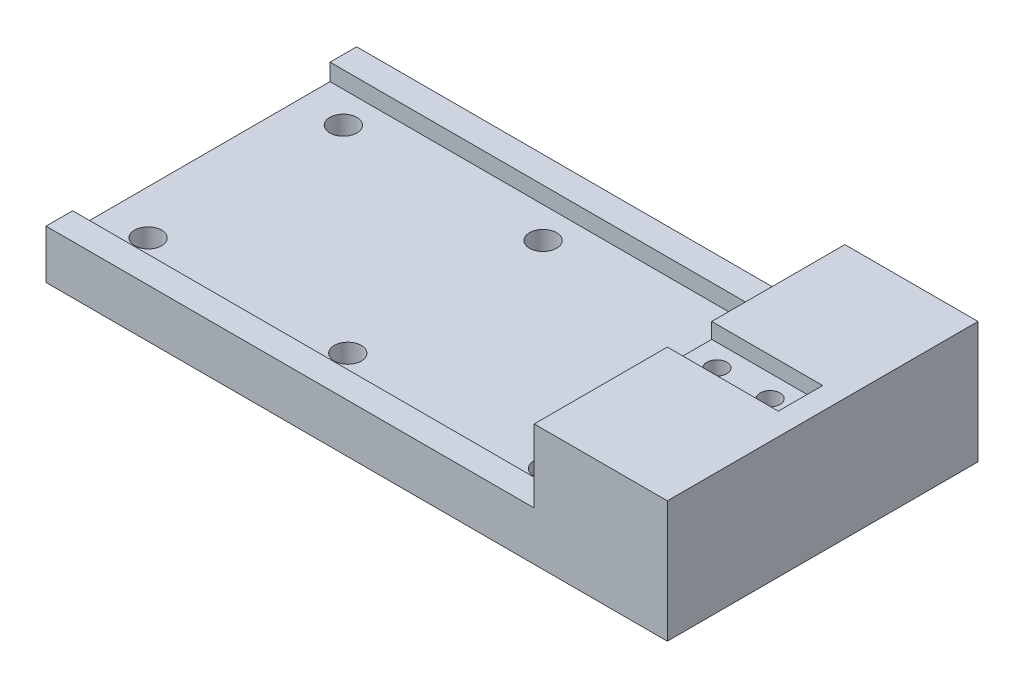
SolidWorks part; units mm, degrees
note: The reader was unsure of these and kept them because the rebuilt part matched: shared geometry of "Esquisse12<3>".
ref_plane "Plan de face" through (0, 0, 0) normal (0, 0, 1) x (1, 0, 0)
ref_plane "Plan de dessus" through (0, 0, 0) normal (0, 1, 0) x (1, 0, 0)
ref_plane "Plan de droite" through (0, 0, 0) normal (1, 0, 0) x (0, 0, -1)
sketch "Esquisse1" plane through (0, 0, 0) normal (0, 0, 1) x (1, 0, 0)
  line L1 (-70, 5.5) -> (70, 5.5)
  line L2 (-70, 5.5) -> (-70, -5.5)
  line L3 (-70, -5.5) -> (70, -5.5)
  line L4 (70, 5.5) -> (70, -5.5)
  line L5 (-70, 5.5) -> (70, -5.5) construction
  line L6 (-70, -5.5) -> (70, 5.5) construction
  point P0 (0, 0)
  dimension "D1" = 11
  dimension "D2" = 140
extrude "Boss.-Extru.1" add sketch "Esquisse1" along normal blind 70
chamfer "Chanfrein1" [suppressed] distance 20 angle 75
sketch "Esquisse2" plane through (-70, 0, 0) normal (-1, 0, 0) x (0, 0, 1)
  line L0 (70, 5.5) -> (0, 5.5) construction
  line L1 (25.6, 5.5) -> (44.4, 5.5)
  arc A0 (25.6, 5.5) -> (44.4, 5.5) centre (35, 5.5) ccw
  dimension "D1" = 9.4
extrude "Enlèv. mat.-Extru.1" cut sketch "Esquisse2" against normal offset from surface (110 mm away) 30 up to face at (70, 0, 35)
sketch "Esquisse4" plane through (0, 5.5, 0) normal (0, 1, 0) x (1, 0, 0)
  line L0 (-69, -18.1) -> (-69, -24.1)
  line L1 (-9, -18.1) -> (-9, -24.1)
  line L2 (-70, -35) -> (70, -35) construction
  line L3 (-70, -25.6) -> (-70, -44.4) construction
  line L4 (70, -70) -> (70, 0) construction
  line L5 (-70, -25.6) -> (-70, 0) construction
  line L6 (-69, -51.9) -> (-69, -45.9)
  line L7 (-68, -18.1) -> (-68, -24.1)
  line L8 (-68, -51.9) -> (-68, -45.9)
  line L9 (-67, -18.1) -> (-67, -24.1)
  line L10 (-67, -51.9) -> (-67, -45.9)
  line L11 (-66, -18.1) -> (-66, -24.1)
  line L12 (-66, -51.9) -> (-66, -45.9)
  line L13 (-65, -18.1) -> (-65, -24.1)
  line L14 (-65, -51.9) -> (-65, -45.9)
  line L15 (-64, -18.1) -> (-64, -24.1)
  line L16 (-64, -51.9) -> (-64, -45.9)
  line L17 (-63, -18.1) -> (-63, -24.1)
  line L18 (-63, -51.9) -> (-63, -45.9)
  line L19 (-62, -18.1) -> (-62, -24.1)
  line L20 (-62, -51.9) -> (-62, -45.9)
  line L21 (-61, -18.1) -> (-61, -24.1)
  line L22 (-61, -51.9) -> (-61, -45.9)
  line L23 (-60, -18.1) -> (-60, -24.1)
  line L24 (-60, -51.9) -> (-60, -45.9)
  line L25 (-59, -18.1) -> (-59, -24.1)
  line L26 (-59, -51.9) -> (-59, -45.9)
  line L27 (-58, -18.1) -> (-58, -24.1)
  line L28 (-58, -51.9) -> (-58, -45.9)
  line L29 (-57, -18.1) -> (-57, -24.1)
  line L30 (-57, -51.9) -> (-57, -45.9)
  line L31 (-56, -18.1) -> (-56, -24.1)
  line L32 (-56, -51.9) -> (-56, -45.9)
  line L33 (-55, -18.1) -> (-55, -24.1)
  line L34 (-55, -51.9) -> (-55, -45.9)
  line L35 (-54, -18.1) -> (-54, -24.1)
  line L36 (-54, -51.9) -> (-54, -45.9)
  line L37 (-53, -18.1) -> (-53, -24.1)
  line L38 (-53, -51.9) -> (-53, -45.9)
  line L39 (-52, -18.1) -> (-52, -24.1)
  line L40 (-52, -51.9) -> (-52, -45.9)
  line L41 (-51, -18.1) -> (-51, -24.1)
  line L42 (-51, -51.9) -> (-51, -45.9)
  line L43 (-50, -18.1) -> (-50, -24.1)
  line L44 (-50, -51.9) -> (-50, -45.9)
  line L45 (-49, -18.1) -> (-49, -24.1)
  line L46 (-49, -51.9) -> (-49, -45.9)
  line L47 (-48, -18.1) -> (-48, -24.1)
  line L48 (-48, -51.9) -> (-48, -45.9)
  line L49 (-47, -18.1) -> (-47, -24.1)
  line L50 (-47, -51.9) -> (-47, -45.9)
  line L51 (-46, -18.1) -> (-46, -24.1)
  line L52 (-46, -51.9) -> (-46, -45.9)
  line L53 (-45, -18.1) -> (-45, -24.1)
  line L54 (-45, -51.9) -> (-45, -45.9)
  line L55 (-44, -18.1) -> (-44, -24.1)
  line L56 (-44, -51.9) -> (-44, -45.9)
  line L57 (-43, -18.1) -> (-43, -24.1)
  line L58 (-43, -51.9) -> (-43, -45.9)
  line L59 (-42, -18.1) -> (-42, -24.1)
  line L60 (-42, -51.9) -> (-42, -45.9)
  line L61 (-41, -18.1) -> (-41, -24.1)
  line L62 (-41, -51.9) -> (-41, -45.9)
  line L63 (-40, -18.1) -> (-40, -24.1)
  line L64 (-40, -51.9) -> (-40, -45.9)
  line L65 (-39, -18.1) -> (-39, -24.1)
  line L66 (-39, -51.9) -> (-39, -45.9)
  line L67 (-38, -18.1) -> (-38, -24.1)
  line L68 (-38, -51.9) -> (-38, -45.9)
  line L69 (-37, -18.1) -> (-37, -24.1)
  line L70 (-37, -51.9) -> (-37, -45.9)
  line L71 (-36, -18.1) -> (-36, -24.1)
  line L72 (-36, -51.9) -> (-36, -45.9)
  line L73 (-35, -18.1) -> (-35, -24.1)
  line L74 (-35, -51.9) -> (-35, -45.9)
  line L75 (-34, -18.1) -> (-34, -24.1)
  line L76 (-34, -51.9) -> (-34, -45.9)
  line L77 (-33, -18.1) -> (-33, -24.1)
  line L78 (-33, -51.9) -> (-33, -45.9)
  line L79 (-32, -18.1) -> (-32, -24.1)
  line L80 (-32, -51.9) -> (-32, -45.9)
  line L81 (-31, -18.1) -> (-31, -24.1)
  line L82 (-31, -51.9) -> (-31, -45.9)
  line L83 (-30, -18.1) -> (-30, -24.1)
  line L84 (-30, -51.9) -> (-30, -45.9)
  line L85 (-29, -18.1) -> (-29, -24.1)
  line L86 (-29, -51.9) -> (-29, -45.9)
  line L87 (-28, -18.1) -> (-28, -24.1)
  line L88 (-28, -51.9) -> (-28, -45.9)
  line L89 (-27, -18.1) -> (-27, -24.1)
  line L90 (-27, -51.9) -> (-27, -45.9)
  line L91 (-26, -18.1) -> (-26, -24.1)
  line L92 (-26, -51.9) -> (-26, -45.9)
  line L93 (-25, -18.1) -> (-25, -24.1)
  line L94 (-25, -51.9) -> (-25, -45.9)
  line L95 (-24, -18.1) -> (-24, -24.1)
  line L96 (-24, -51.9) -> (-24, -45.9)
  line L97 (-23, -18.1) -> (-23, -24.1)
  line L98 (-23, -51.9) -> (-23, -45.9)
  line L99 (-22, -18.1) -> (-22, -24.1)
  line L100 (-22, -51.9) -> (-22, -45.9)
  line L101 (-21, -18.1) -> (-21, -24.1)
  line L102 (-21, -51.9) -> (-21, -45.9)
  line L103 (-20, -18.1) -> (-20, -24.1)
  line L104 (-20, -51.9) -> (-20, -45.9)
  line L105 (-19, -18.1) -> (-19, -24.1)
  line L106 (-19, -51.9) -> (-19, -45.9)
  line L107 (-18, -18.1) -> (-18, -24.1)
  line L108 (-18, -51.9) -> (-18, -45.9)
  line L109 (-17, -18.1) -> (-17, -24.1)
  line L110 (-17, -51.9) -> (-17, -45.9)
  line L111 (-16, -18.1) -> (-16, -24.1)
  line L112 (-16, -51.9) -> (-16, -45.9)
  line L113 (-15, -18.1) -> (-15, -24.1)
  line L114 (-15, -51.9) -> (-15, -45.9)
  line L115 (-14, -18.1) -> (-14, -24.1)
  line L116 (-14, -51.9) -> (-14, -45.9)
  line L117 (-13, -18.1) -> (-13, -24.1)
  line L118 (-13, -51.9) -> (-13, -45.9)
  line L119 (-12, -18.1) -> (-12, -24.1)
  line L120 (-12, -51.9) -> (-12, -45.9)
  line L121 (-11, -18.1) -> (-11, -24.1)
  line L122 (-11, -51.9) -> (-11, -45.9)
  line L123 (-10, -18.1) -> (-10, -24.1)
  line L124 (-10, -51.9) -> (-10, -45.9)
  line L125 (40, -25.6) -> (-70, -25.6) construction
  line L126 (-9, -51.9) -> (-9, -45.9)
  line L127 (-8, -18.1) -> (-8, -24.1)
  line L128 (-8, -51.9) -> (-8, -45.9)
  line L129 (-7, -18.1) -> (-7, -24.1)
  line L130 (-7, -51.9) -> (-7, -45.9)
  line L131 (-6, -18.1) -> (-6, -24.1)
  line L132 (-6, -51.9) -> (-6, -45.9)
  line L133 (-5, -18.1) -> (-5, -24.1)
  line L134 (-5, -51.9) -> (-5, -45.9)
  line L135 (-4, -18.1) -> (-4, -24.1)
  line L136 (-4, -51.9) -> (-4, -45.9)
  line L137 (-3, -18.1) -> (-3, -24.1)
  line L138 (-3, -51.9) -> (-3, -45.9)
  line L139 (-2, -18.1) -> (-2, -24.1)
  line L140 (-2, -51.9) -> (-2, -45.9)
  line L141 (-1, -18.1) -> (-1, -24.1)
  line L142 (-1, -51.9) -> (-1, -45.9)
  line L143 (0, -18.1) -> (0, -24.1)
  line L144 (0, -51.9) -> (0, -45.9)
  line L145 (1, -18.1) -> (1, -24.1)
  line L146 (1, -51.9) -> (1, -45.9)
  line L147 (2, -18.1) -> (2, -24.1)
  line L148 (2, -51.9) -> (2, -45.9)
  line L149 (3, -18.1) -> (3, -24.1)
  line L150 (3, -51.9) -> (3, -45.9)
  line L151 (4, -18.1) -> (4, -24.1)
  line L152 (4, -51.9) -> (4, -45.9)
  line L153 (5, -18.1) -> (5, -24.1)
  line L154 (5, -51.9) -> (5, -45.9)
  line L155 (6, -18.1) -> (6, -24.1)
  line L156 (6, -51.9) -> (6, -45.9)
  line L157 (7, -18.1) -> (7, -24.1)
  line L158 (7, -51.9) -> (7, -45.9)
  line L159 (8, -18.1) -> (8, -24.1)
  line L160 (8, -51.9) -> (8, -45.9)
  line L161 (9, -18.1) -> (9, -24.1)
  line L162 (9, -51.9) -> (9, -45.9)
  line L163 (10, -18.1) -> (10, -24.1)
  line L164 (10, -51.9) -> (10, -45.9)
  line L165 (11, -18.1) -> (11, -24.1)
  line L166 (11, -51.9) -> (11, -45.9)
  line L167 (12, -18.1) -> (12, -24.1)
  line L168 (12, -51.9) -> (12, -45.9)
  line L169 (13, -18.1) -> (13, -24.1)
  line L170 (13, -51.9) -> (13, -45.9)
  line L171 (14, -18.1) -> (14, -24.1)
  line L172 (14, -51.9) -> (14, -45.9)
  line L173 (15, -18.1) -> (15, -24.1)
  line L174 (15, -51.9) -> (15, -45.9)
  line L175 (16, -18.1) -> (16, -24.1)
  line L176 (16, -51.9) -> (16, -45.9)
  line L177 (17, -18.1) -> (17, -24.1)
  line L178 (17, -51.9) -> (17, -45.9)
  line L179 (18, -18.1) -> (18, -24.1)
  line L180 (18, -51.9) -> (18, -45.9)
  line L181 (19, -18.1) -> (19, -24.1)
  line L182 (19, -51.9) -> (19, -45.9)
  line L183 (20, -18.1) -> (20, -24.1)
  line L184 (20, -51.9) -> (20, -45.9)
  dimension "D1" = 6
  dimension "D2" = 1
  dimension "D4" = 1
  dimension "D5" = 1.5
  dimension "D3" = 90
sketch "Esquisse6" plane through (0, 5.5, 0) normal (0, 1, 0) x (1, 0, 0)
  line L0 (70, 0) -> (-70, 0) construction
  line L1 (70, -70) -> (40, -70)
  line L2 (70, -70) -> (70, 0)
  line L3 (70, 0) -> (40, 0)
  line L4 (40, -70) -> (40, 0)
  line L5 (40, -25.6) -> (40, -44.4) construction
sketch "Esquisse7" plane through (40, 0, 0) normal (-1, 0, 0) x (0, 0, 1)
  line L1 (30, 21.9) -> (40, 21.9) construction
  line L2 (30, 21.9) -> (30, 7.5) construction
  line L3 (30, 7.5) -> (40, 7.5) construction
  line L4 (40, 21.9) -> (40, 7.5) construction
  line L5 (30, 21.9) -> (40, 7.5) construction
  line L7 (25.6, 5.5) -> (44.4, 5.5) construction
  line L8 (35, 23.9) -> (35, 5.5) construction
  circle A0 centre (35, 14.7) radius 9.2
  point P11 (35, 14.7)
  dimension "D4" = 18.4
  dimension "D2" = 10
  dimension "D3" = 14.4
extrude "Boss.-Extru.3" add sketch "Esquisse6" along normal up to vertex (16.4 mm away) contours L4 L3 L2 L1 up to point (40, 21.9, 40)
sketch "Esquisse9" plane through (40, 0, 0) normal (-1, 0, 0) x (0, 0, 1)
  line L0 (30, 21.9) -> (30, 7.5) construction
  line L1 (30, 11) -> (40, 11)
  line L2 (30, 11) -> (30, 7.5)
  line L3 (30, 7.5) -> (40, 7.5)
  line L4 (40, 11) -> (40, 7.5)
  line L5 (30, 14.7) -> (40, 14.7) construction
  line L6 (40, 21.9) -> (40, 7.5) construction
  line L7 (30, 18.4) -> (30, 21.9)
  line L8 (30, 21.9) -> (40, 21.9)
  line L9 (40, 18.4) -> (40, 21.9)
  line L10 (30, 18.4) -> (40, 18.4)
  dimension "D1" = 3.5
extrude "Enlèv. mat.-Extru.3" cut sketch "Esquisse9" against normal blind 25
sketch "Esquisse10" plane through (0, 18.4, 0) normal (0, 1, 0) x (1, 0, 0)
  line L0 (39.8, -30) -> (39.8, -40) construction
  line L1 (65, -30) -> (40, -30) construction
  line L2 (65, -40) -> (40, -40) construction
  line L3 (65, -40) -> (40, -40) construction
  line L5 (40, -30) -> (40, -40) construction
  line L6 (39.8, -30) -> (52.5, -40) construction
  circle A0 centre (46.15, -35) radius 2.25
  circle A1 centre (58.15, -35) radius 2.25
  point P11 (46.15, -35)
  dimension "D2" = 4.5
  dimension "D3" = 12
  dimension "D1" = 0.2
extrude "Enlèv. mat.-Extru.4" cut sketch "Esquisse10" against normal offset from surface (10.8 mm away) 0.1 contours A1 | A0 up to face at (52.5, 7.5, 35)
sketch "Esquisse11" plane through (0, 5.5, 0) normal (0, 1, 0) x (1, 0, 0)
  line L0 (40, -35) -> (-70, -35) construction
  line L1 (14.9, -24.6) -> (20.1, -24.6)
  line L2 (14.9, -24.6) -> (14.9, -45.4)
  line L3 (14.9, -45.4) -> (20.1, -45.4)
  line L4 (20.1, -24.6) -> (20.1, -45.4)
  line L5 (40, -30) -> (40, -40) construction
  line L6 (-70, -25.6) -> (-70, -44.4) construction
  line L7 (14.9, -24.6) -> (20.1, -45.4) construction
  line L8 (40, -25.6) -> (-70, -25.6) construction
  line L9 (40, -30) -> (40, 0) construction
  line L10 (-15, -24.6) -> (-9.8, -24.6)
  line L11 (-9.8, -24.6) -> (-9.8, -45.4)
  line L12 (-15, -45.4) -> (-9.8, -45.4)
  line L13 (-15, -24.6) -> (-15, -45.4)
  line L14 (-44.9, -24.6) -> (-39.7, -24.6)
  line L15 (-39.7, -24.6) -> (-39.7, -45.4)
  line L16 (-44.9, -45.4) -> (-39.7, -45.4)
  line L17 (-44.9, -24.6) -> (-44.9, -45.4)
  line L18 (-74.8, -24.6) -> (-69.6, -24.6)
  line L19 (-69.6, -24.6) -> (-69.6, -45.4)
  line L20 (-74.8, -45.4) -> (-69.6, -45.4)
  line L21 (-74.8, -24.6) -> (-74.8, -45.4)
  point P10 (17.5, -35)
  dimension "D1" = 1
  dimension "D2" = 5.2
  dimension "D3" = 19.9
  dimension "D4" = 4
  dimension "D5" = 29.9
sketch "Esquisse12" plane through (0, 5.5, 0) normal (0, 1, 0) x (1, 0, 0)
  line L0 (-70, -25.6) -> (-70, 0) construction
  line L1 (-70, -6) -> (40, -6)
  line L2 (-70, -6) -> (-70, -35)
  line L3 (-70, -35) -> (40, -35)
  line L4 (40, -6) -> (40, -35)
  line L7 (-70, -35) -> (40, -35) construction
  line L8 (-70, -25.6) -> (-70, -44.4) construction
  line L9 (40, -30) -> (40, -40) construction
  line L10 (40, 0) -> (-70, 0) construction
  line L11 (-70, -35) -> (40, -35)
  line L12 (40, -64) -> (40, -35)
  line L13 (-70, -64) -> (40, -64)
  line L14 (-70, -64) -> (-70, -35)
  line L15 (40, -30) -> (40, 0) construction
  circle A0 centre (-60, -13) radius 3.05
  circle A1 centre (-15, -13) radius 3.05
  circle A2 centre (30, -13) radius 3.05
  circle A3 centre (-60, -57) radius 3.05
  circle A4 centre (-15, -57) radius 3.05
  circle A5 centre (30, -57) radius 3.05
  dimension "D2" = 6.1
  dimension "D3" = 45
  dimension "D4" = 45
  dimension "D6" = 7
  dimension "D1" = 6
  dimension "D5" = 10
extrude "Enlèv. mat.-Extru.6" cut sketch "Esquisse12" against normal offset from surface (3.8 mm away) 5.8
extrude "Enlèv. mat.-Extru.7" cut sketch "Esquisse12<3>" against normal blind 12 contours A0 | A1 | A2 | A5 | A3 | A4
sketch "Esquisse12<3>" plane through (0, 5.5, 0) normal (0, 1, 0) x (1, 0, 0) same geometry as "Esquisse12"
sketch "Esquisse13" plane through (0, 1.7, 0) normal (0, 1, 0) x (1, 0, 0)
  line L4 (-70, -26.4023) -> (-70, -43.5977)
  line L5 (-70, -43.5977) -> (40, -43.5977)
  line L6 (40, -43.5977) -> (40, -26.4023)
  line L7 (40, -26.4023) -> (-70, -26.4023)
  line L8 (-70, -26.4023) -> (-70, -43.5977)
  line L9 (-70, -43.5977) -> (40, -43.5977)
  line L10 (40, -43.5977) -> (40, -26.4023)
  line L11 (40, -26.4023) -> (-70, -26.4023)
  dimension "D1" = 0
extrude "Boss.-Extru.4" add sketch "Esquisse13" against normal up to next
